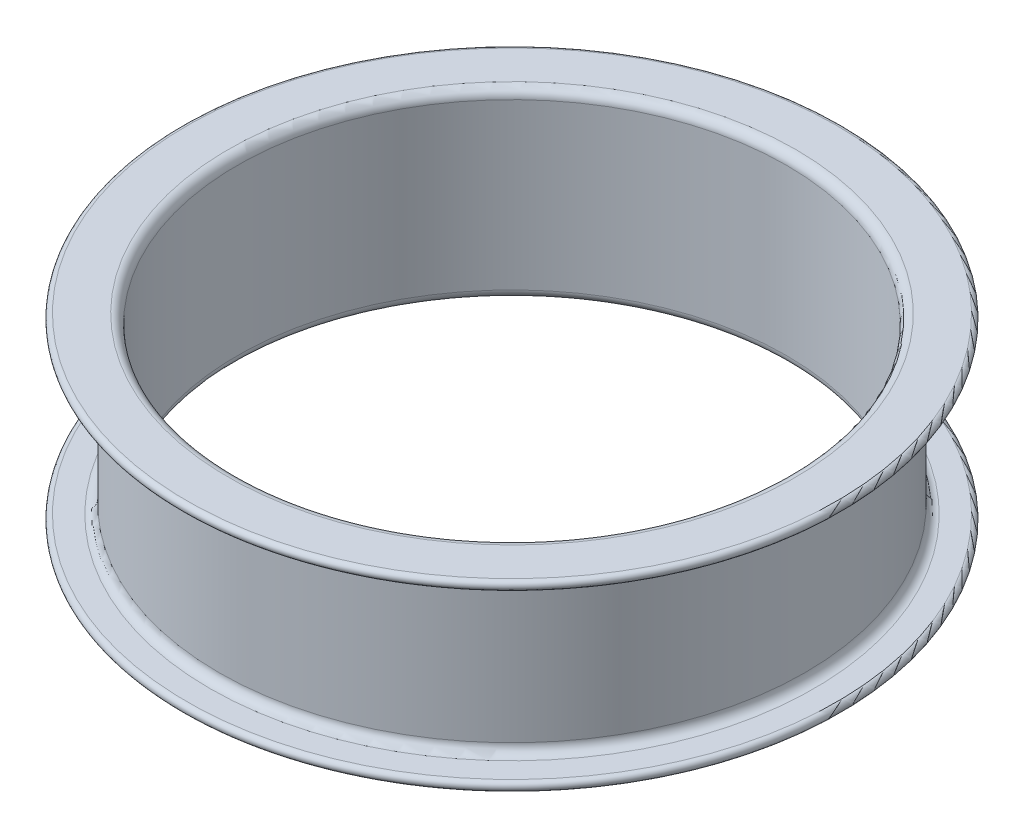
SolidWorks part; units mm, degrees
material "Chrome Stainless Steel"
ref_plane "Front Plane" through (0, 0, 0) normal (1, 0, 0) x (0, 1, 0)
ref_plane "Top Plane" through (0, 0, 0) normal (0, 0, 1) x (0, 1, 0)
ref_plane "Right Plane" through (0, 0, 0) normal (0, 1, 0) x (-1, 0, 0)
sketch "Sketch2" plane through (0, 0, 0) normal (1, 0, 0) x (0, 1, 0)
  line L0 (0, 20.6942) -> (0, -18.6446) construction
  line L1 (-17.2757, 0) -> (16.3772, 0) construction
  line L2 (-5, 15) -> (-5, 18)
  line L3 (-5, 18) -> (-4.5, 18)
  line L4 (-4.5, 18) -> (-4.5, 16)
  line L5 (-4.5, 16) -> (4.5, 16)
  line L6 (4.5, 16) -> (4.5, 18)
  line L7 (4.5, 18) -> (5, 18)
  line L8 (5, 18) -> (5, 15)
  line L9 (5, 15) -> (-5, 15)
  point P14 (0, 15)
  point P15 (0, 16)
  dimension "D1" = 16
  dimension "D2" = 10
  dimension "D3" = 9
  dimension "D4" = 30
  dimension "D5" = 36
revolve "Revolve1" add sketch "Sketch2" angle 360 about L1
fillet "Fillet1" radius 0.5 4 edges at (0, -4.5, -16) (0, 5, -15) (0, 4.5, -16) (0, -5, -15)
fillet "Fillet2" 2 edges at (0, 5, -18) (0, 4.5, -18) type full round first side face at (0, 5, -15.5) second side face at (0, 4.5, 16.5) middle face at (0, 4.5, -18)
fillet "Fillet3" 2 edges at (0, -4.5, -18) (0, -5, -18) type full round first side face at (0, -4.5, -16.5) second side face at (0, -5, 15.5) middle face at (0, -5, -18)
